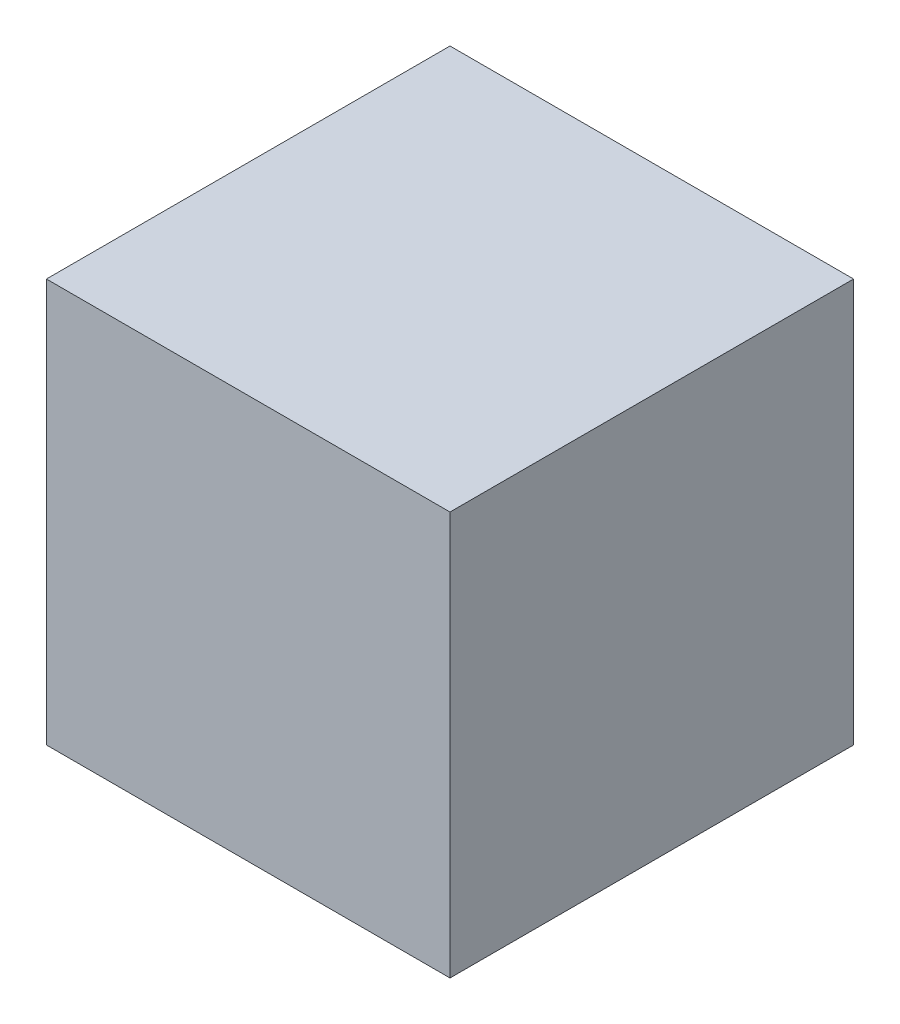
SolidWorks part; units mm, degrees
ref_plane "Front Plane" through (0, 0, 0) normal (0, 0, 1) x (1, 0, 0)
ref_plane "Top Plane" through (0, 0, 0) normal (0, 1, 0) x (1, 0, 0)
ref_plane "Right Plane" through (0, 0, 0) normal (1, 0, 0) x (0, 0, -1)
sketch "Sketch1" plane through (0, 0, 0) normal (0, 1, 0) x (1, 0, 0)
  line L1 (-5, -5) -> (5, -5)
  line L2 (-5, -5) -> (-5, 5)
  line L3 (-5, 5) -> (5, 5)
  line L4 (5, -5) -> (5, 5)
  dimension "D1" = 10
  dimension "D2" = 10
  dimension "D3" = 5
  dimension "D4" = 5
extrude "Boss-Extrude1" add sketch "Sketch1" along normal blind 5 and the other way blind 5
ref_plane "Plane1" through (0, 0, 0) normal (0, 0, 1) x (1, 0, 0)
ref_plane "Plane2" through (0, 0, 0) normal (1, 0, 0) x (0, 0, -1)
ref_plane "Plane3" through (0, 0, 0) normal (0, 1, 0) x (1, 0, 0)
ref_axis "Zaxis" through (0, 10.5, 0) along (0, -1, 0)
ref_axis "Yaxis" through (5.5, 0, 0) along (-1, 0, 0)
ref_axis "Xaxis" through (0, 0, 5.5) along (0, 0, -1)
